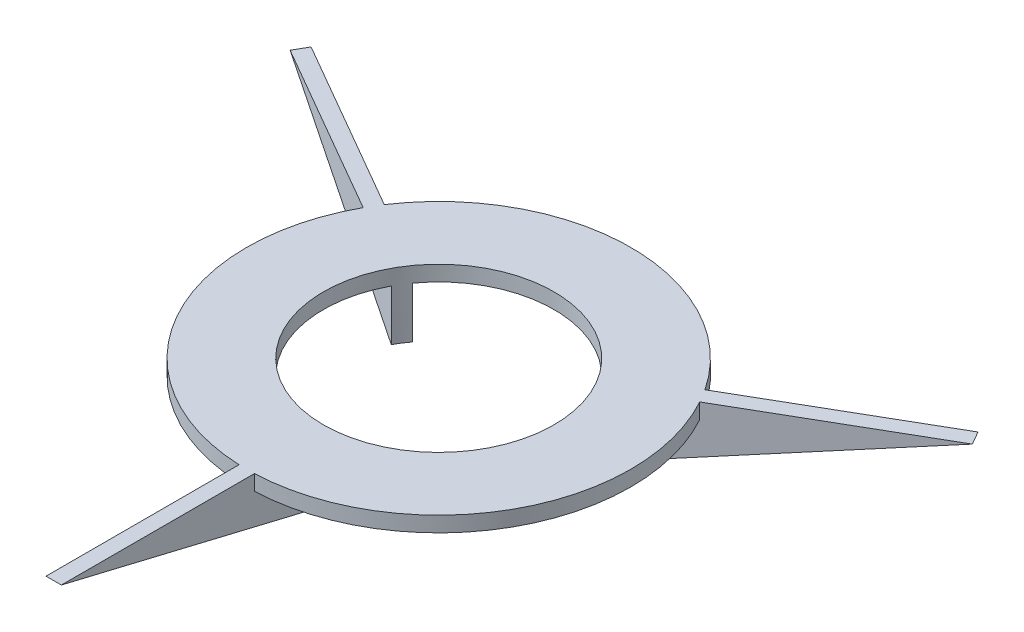
SolidWorks part; units mm, degrees
material "Galvanized Steel"
ref_plane "Front Plane" through (0, 0, 0) normal (0, 0, 1) x (1, 0, 0)
ref_plane "Top Plane" through (0, 0, 0) normal (0, 1, 0) x (1, 0, 0)
ref_plane "Right Plane" through (0, 0, 0) normal (1, 0, 0) x (0, 0, -1)
sketch "Sketch1" plane through (0, 0, 0) normal (0, 0, 1) x (1, 0, 0)
  line L0 (0, 0) -> (0, 50.2347) construction
  line L2 (16.51, 0) -> (42.4155, 10.4665)
  line L3 (42.4155, 10.4665) -> (16.51, 10.4665)
  line L4 (16.51, 10.4665) -> (16.51, 0)
  dimension "D1" = 33.02
  dimension "D2" = 68
  dimension "D3" = 27.94
revolve "Revolve1" [suppressed] add sketch "Sketch1" angle 360 about L0
sketch "Sketch2" plane through (0, 0, 0) normal (0, 1, 0) x (1, 0, 0)
  line L0 (-1.27, 0) -> (0, 2.1997)
  line L1 (0, 2.1997) -> (1.27, 0)
  line L2 (1.27, 0) -> (-1.27, 0)
  dimension "D1" = 2.54
extrude "Boss-Extrude1" add sketch "Sketch2" along normal blind 15.24
sketch "Sketch3" plane through (0, 0, 0) normal (1, 0, 0) x (0, 0, -1)
  line L0 (0, 15.24) -> (-63.627, 15.24)
  line L1 (-63.627, 15.24) -> (0, 0)
  line L2 (-28.7672, 6.8903) -> (-7.5582, 6.8903) construction
  line L3 (-7.5582, 6.8903) -> (-7.5582, 1.8103) construction
  line L6 (0, 0) -> (2.1997, 0)
  line L7 (2.1997, 0) -> (2.1997, 15.24)
  line L8 (2.1997, 15.24) -> (0, 15.24)
  line L9 (0, 15.24) -> (0, 0)
  line L13 (0, 15.24) -> (0, 0)
  dimension "D1" = 5.08
  dimension "D3" = 21.209
  dimension "D2" = 0
extrude "Boss-Extrude2" add sketch "Sketch3" along normal mid plane 2.54
ref_point "Point1"
ref_axis "Axis1" through (0, 0, -0.7332) along (0, -1, 0)
pattern_circular "CirPattern1" count 3 every 120 about axis through (0, 0, -0.7332) along (0, -1, 0) of "Boss-Extrude2" reverse direction yes
sketch "Sketch4" plane through (0, 15.24, 0) normal (0, 1, 0) x (1, 0, 0)
  circle A0 centre (0, 0) radius 19.05
  circle A1 centre (0, 0) radius 31.75
  dimension "D1" = 38.1
  dimension "D2" = 12.7
extrude "Boss-Extrude3" add sketch "Sketch4" against normal blind 2.54
sketch "Sketch5" plane through (0, 15.24, 0) normal (0, 1, 0) x (1, 0, 0)
  arc A0 (15.4626, 11.127) -> (-15.4626, 11.127) centre (0, 0) ccw construction
  arc A1 (1.27, -19.0076) -> (16.8061, 8.9698) centre (0, 0) ccw construction
  arc A2 (-16.8061, 8.9698) -> (-1.27, -19.0076) centre (0, 0) ccw construction
  arc A3 (15.4626, 11.127) -> (-15.4626, 11.127) centre (0, 0) ccw
  arc A4 (1.27, -19.0076) -> (16.8061, 8.9698) centre (0, 0) ccw
  arc A5 (-16.8061, 8.9698) -> (-1.27, -19.0076) centre (0, 0) ccw
  circle A6 centre (0, 0) radius 19.05
extrude "Cut-Extrude1" cut sketch "Sketch5" against normal through all contours A6
